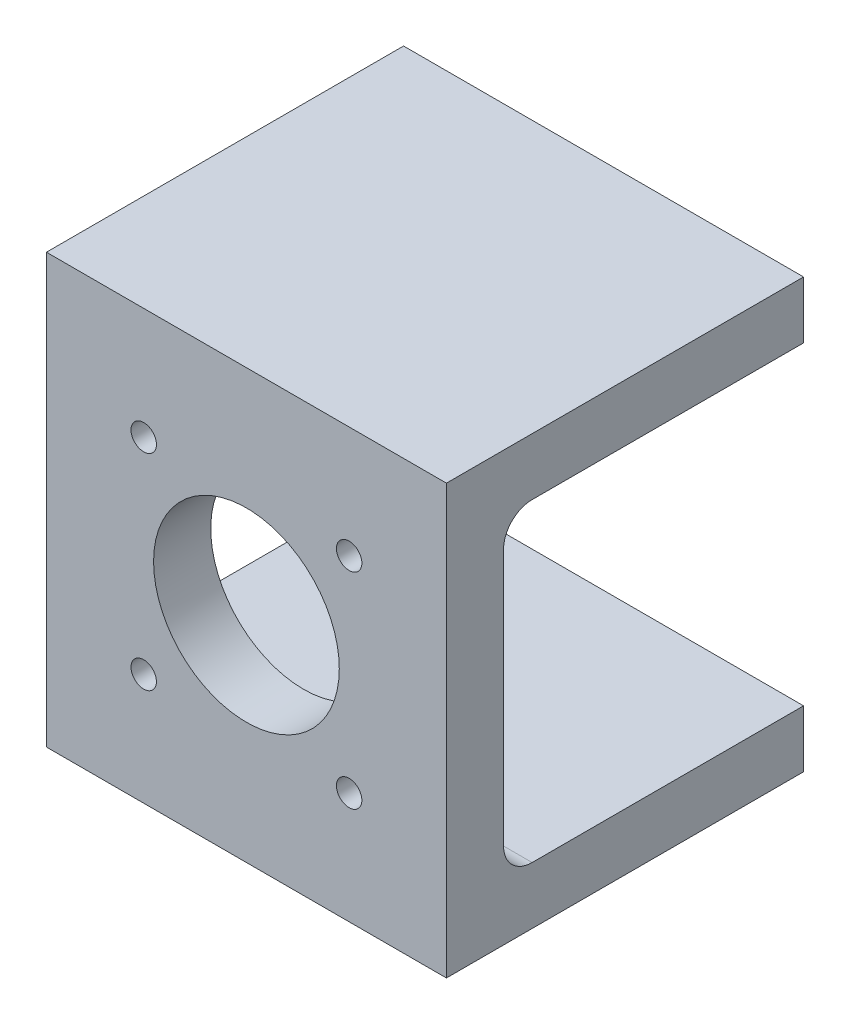
SolidWorks part; units mm, degrees
material "ABS"
ref_plane "Front Plane" through (0, 0, 0) normal (0, 0, 1) x (1, 0, 0)
ref_plane "Top Plane" through (0, 0, 0) normal (0, 1, 0) x (1, 0, 0)
ref_plane "Right Plane" through (0, 0, 0) normal (1, 0, 0) x (0, 0, -1)
sketch "Sketch1" plane through (0, 0, 0) normal (0, 0, 1) x (1, 0, 0)
  line L1 (-17.78, -19.05) -> (17.78, -19.05)
  line L2 (-17.78, -19.05) -> (-17.78, 19.05)
  line L3 (-17.78, 19.05) -> (17.78, 19.05)
  line L4 (17.78, -19.05) -> (17.78, 19.05)
  line L5 (-17.78, -19.05) -> (17.78, 19.05) construction
  line L6 (-17.78, 19.05) -> (17.78, -19.05) construction
  line L7 (-9.1313, -9.1313) -> (9.1313, -9.1313) construction
  line L8 (-9.1313, -9.1313) -> (-9.1313, 9.1313) construction
  line L9 (-9.1313, 9.1313) -> (9.1313, 9.1313) construction
  line L10 (9.1313, -9.1313) -> (9.1313, 9.1313) construction
  line L11 (-9.1313, -9.1313) -> (9.1313, 9.1313) construction
  line L12 (-9.1313, 9.1313) -> (9.1313, -9.1313) construction
  circle A0 centre (0, 0) radius 8.255
  circle A1 centre (-9.1313, 9.1313) radius 1.1303
  circle A2 centre (9.1313, 9.1313) radius 1.1303
  circle A3 centre (-9.1313, -9.1313) radius 1.1303
  circle A4 centre (9.1313, -9.1313) radius 1.1303
  point P0 (0, 0)
  dimension "D3" = 16.51
  dimension "D5" = 2.2606
  dimension "D1" = 38.1
  dimension "D2" = 35.56
  dimension "D4" = 18.2626
  dimension "D6" = 18.2626
extrude "Boss-Extrude with 4-40 Tap Drill Holes" add sketch "Sketch1" against normal mid plane 31.75
sketch "Sketch3" plane through (17.78, 0, 0) normal (1, 0, 0) x (0, 0, -1)
  line L0 (15.875, -19.05) -> (15.875, 19.05) construction
  line L1 (15.875, 13.97) -> (-10.795, 13.97)
  line L2 (15.875, 13.97) -> (15.875, -13.97)
  line L3 (15.875, -13.97) -> (-10.795, -13.97)
  line L4 (-10.795, 13.97) -> (-10.795, -13.97)
  line L5 (15.875, 19.05) -> (-15.875, 19.05) construction
  line L6 (15.875, -19.05) -> (-15.875, -19.05) construction
  line L7 (-15.875, -19.05) -> (-15.875, 19.05) construction
  dimension "D1" = 5.08
  dimension "D2" = 5.08
  dimension "D3" = 5.08
extrude "Cut-Extrude1" cut sketch "Sketch3" against normal up to next
fillet "Fillet1" radius 2.54 2 edges at (0, -13.97, 10.795) (0, 13.97, 10.795)
sketch "Sketch5" plane through (0, 19.05, 0) normal (0, 1, 0) x (1, 0, 0)
  line L4 (-17.78, 15.875) -> (-17.78, -8.255)
  line L5 (-17.78, 15.875) -> (-17.78, -8.255)
  line L6 (17.78, -8.255) -> (17.78, 15.875)
  line L7 (17.78, 15.875) -> (-17.78, 15.875)
  line L8 (-17.78, -8.255) -> (17.78, -8.255)
  line L9 (-17.78, -8.255) -> (17.78, -8.255)
  line L10 (17.78, -8.255) -> (17.78, 15.875)
  line L11 (17.78, 15.875) -> (-17.78, 15.875)
  circle A0 centre (-8.89, 10.795) radius 1.65
  circle A1 centre (8.89, 10.795) radius 1.65
  circle A2 centre (8.89, -4.445) radius 1.65
  circle A3 centre (-8.89, -4.445) radius 1.65
  dimension "D2" = 3.3
  dimension "D3" = 8.89
  dimension "D4" = 8.89
  dimension "D5" = 5.08
  dimension "D6" = 3.81
  dimension "D1" = 0
extrude "Clearance Holes for M3 Screw" [suppressed] cut sketch "Sketch5" against normal through all contours A0 | A3 | A2 | A1
